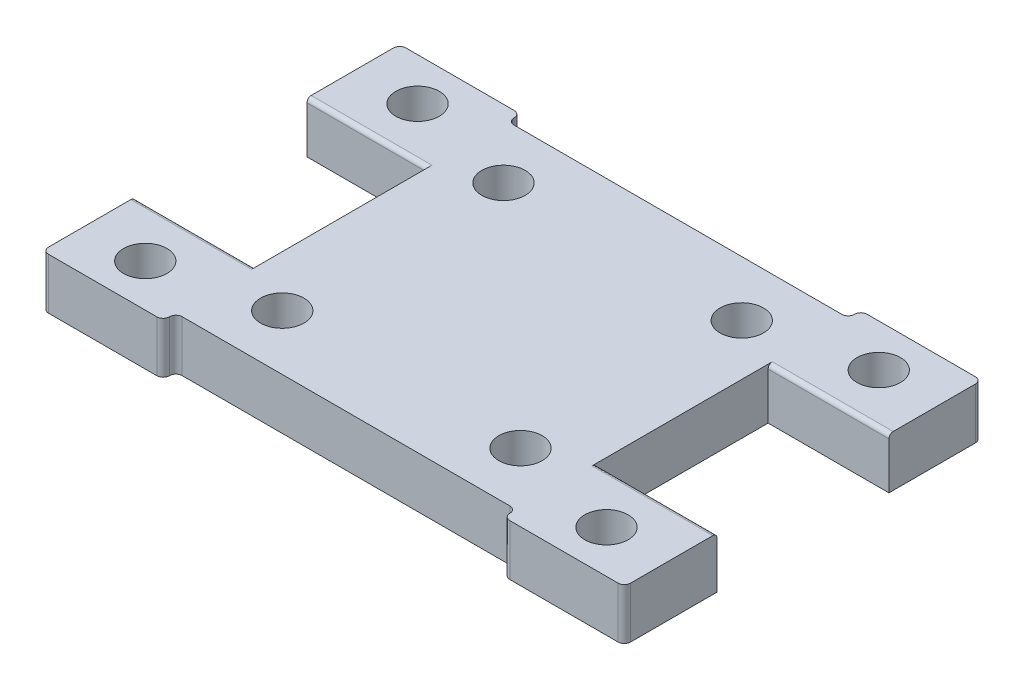
SolidWorks part; units mm, degrees
material "Alloy Steel"
ref_plane "Front Plane" through (0, 0, 0) normal (0, 0, 1) x (1, 0, 0)
ref_plane "Top Plane" through (0, 0, 0) normal (0, 1, 0) x (1, 0, 0)
ref_plane "Right Plane" through (0, 0, 0) normal (1, 0, 0) x (0, 0, -1)
sketch "Sketch1" plane through (0, 0, 0) normal (0, 1, 0) x (1, 0, 0)
  line L0 (20, 19.5) -> (20, -19.5) construction
  line L1 (-19.26, -19.5) -> (19.26, -19.5)
  line L3 (-19.26, 19.5) -> (19.26, 19.5)
  line L5 (20, 20.24) -> (20, 20.26)
  line L7 (20.74, 21) -> (34.2, 21)
  line L8 (20, 19.5) -> (-20, -19.5) construction
  line L9 (-20, 19.5) -> (20, -19.5) construction
  line L10 (0, 0) -> (0, 19.5) construction
  line L11 (0, 0) -> (-20, 0) construction
  line L13 (34.2, -21) -> (20.74, -21)
  line L14 (20, -20.26) -> (20, -20.24)
  line L16 (20, 10.1) -> (34.2, 10.1)
  line L18 (34.2, -10.1) -> (20, -10.1)
  line L19 (20, -10.1) -> (20, 10.1)
  line L20 (-20, 19.5) -> (-20, -19.5) construction
  line L21 (-20, -10.1) -> (-20, 10.1)
  line L22 (-34.2, -10.1) -> (-20, -10.1)
  line L24 (-20, 10.1) -> (-34.2, 10.1)
  line L25 (-20, -20.26) -> (-20, -20.24)
  line L26 (-34.2, -21) -> (-20.74, -21)
  line L28 (-20.74, 21) -> (-34.2, 21)
  line L29 (-20, 20.24) -> (-20, 20.26)
  line L30 (34.2, 10.1) -> (34.2, 21)
  line L31 (34.2, -10.1) -> (34.2, -21)
  line L32 (-34.2, -10.1) -> (-34.2, -21)
  line L33 (-34.2, 10.1) -> (-34.2, 21)
  circle A0 centre (-14, 13) radius 2.55
  circle A1 centre (14, 13) radius 2.55
  circle A2 centre (14, -13) radius 2.55
  circle A3 centre (-14, -13) radius 2.55
  circle A4 centre (27.1, 16) radius 2.55
  circle A5 centre (27.1, -16) radius 2.55
  circle A6 centre (-27.1, -16) radius 2.55
  circle A7 centre (-27.1, 16) radius 2.55
  arc A12 (-20.74, 21) -> (-20, 20.26) centre (-20.74, 20.26) cw
  arc A13 (-20, 20.24) -> (-19.26, 19.5) centre (-19.26, 20.24) ccw
  arc A14 (20, 20.26) -> (20.74, 21) centre (20.74, 20.26) cw
  arc A15 (19.26, 19.5) -> (20, 20.24) centre (19.26, 20.24) ccw
  arc A16 (19.26, -19.5) -> (20, -20.24) centre (19.26, -20.24) cw
  arc A17 (20.74, -21) -> (20, -20.26) centre (20.74, -20.26) cw
  arc A18 (-20, -20.26) -> (-20.74, -21) centre (-20.74, -20.26) cw
  arc A19 (-19.26, -19.5) -> (-20, -20.24) centre (-19.26, -20.24) ccw
  point P0 (0, 0)
  point P46 (27.1, 10.1)
  point P48 (36, 21)
  point P51 (36, -21)
  point P54 (-36, -21)
  point P57 (-36, 21)
  point P60 (-20, 21)
  point P66 (20, 21)
  point P75 (20, -21)
  point P78 (-20, -21)
  dimension "D5" = 5.1
  dimension "D12" = 20.2
  dimension "D9" = 5.1
  dimension "D1" = 1.5
  dimension "D2" = 39
  dimension "D3" = 40
  dimension "D4" = 1.5
  dimension "D6" = 14
  dimension "D7" = 6.5
  dimension "D8" = 16
  dimension "D10" = 16
  dimension "D11" = 14.2
extrude "Boss-Extrude1" add sketch "Sketch1" along normal blind 6
fillet "Fillet1" radius 0.74 4 edges at (-34.2, 3, -21) (-34.2, 3, 21) (34.2, 3, 21) (34.2, 3, -21)
fillet "Fillet2" radius 0.5 4 edges at (-27.1, 6, -10.1) (-27.1, 6, 10.1) (27.1, 6, -10.1) (27.1, 6, 10.1)
